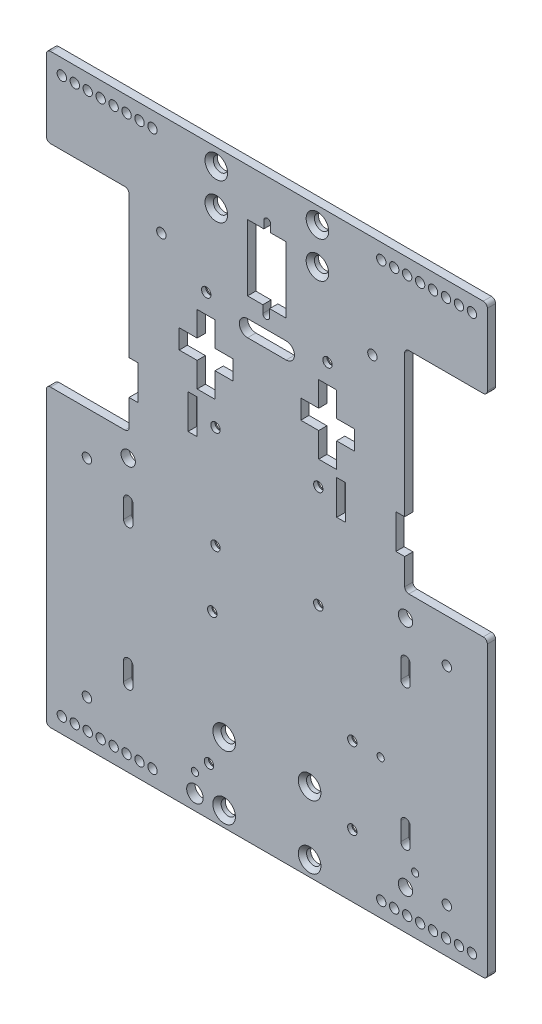
SolidWorks part; units mm, degrees
ref_plane "Front Plane" through (0, 0, 0) normal (0, 0, 1) x (1, 0, 0)
ref_plane "Top Plane" through (0, 0, 0) normal (0, 1, 0) x (1, 0, 0)
ref_plane "Right Plane" through (0, 0, 0) normal (1, 0, 0) x (0, 0, -1)
sketch "Sketch1" plane through (0, 0, 0) normal (0, 0, 1) x (1, 0, 0)
  line L0 (0, 103.7745) -> (0, -122.5392) construction
  line L1 (-241.098, -9.3824) -> (295.6863, -9.3824) construction
  line L2 (-80, -100.3627) -> (80, -100.3627)
  line L3 (80, -100.3627) -> (80, 6.6373)
  line L4 (80, 6.6373) -> (50, 6.6373)
  line L5 (50, 6.6373) -> (50, 83.1373)
  line L6 (50, 83.1373) -> (80, 83.1373)
  line L7 (80, 83.1373) -> (80, 112.1373)
  line L8 (80, 112.1373) -> (-80, 112.1373)
  line L9 (-80, -100.3627) -> (-80, 6.6373)
  line L10 (-80, 6.6373) -> (-50, 6.6373)
  line L11 (-50, 6.6373) -> (-50, 83.1373)
  line L12 (-50, 83.1373) -> (-80, 83.1373)
  line L13 (-80, 83.1373) -> (-80, 112.1373)
  point P14 (0, -100.3627)
  point P19 (0, 112.1373)
  dimension "D1" = 29
  dimension "D2" = 76.5
  dimension "D3" = 107
  dimension "D4" = 160
  dimension "D5" = 30
  dimension "D6" = 30
extrude "Boss-Extrude1" add sketch "Sketch1" along normal blind 3
sketch "Sketch2" plane through (0, 0, 0) normal (0, 0, -1) x (-1, 0, 0)
  line L0 (0, 75.1311) -> (0, 87.1311) construction
  line L1 (-133.8252, 10.7921) -> (150.4053, 10.7921) construction
  line L2 (-7, 95.0453) -> (-1.3739, 95.0453)
  line L3 (7, 95.0453) -> (7, 71.0453)
  line L4 (7, 71.0453) -> (1.4697, 71.0453)
  line L5 (-7, 95.0453) -> (-7, 71.0453)
  line L7 (-1.3739, 97.7783) -> (-1.3739, 95.0453)
  line L8 (1.0943, 97.7783) -> (1.0943, 95.0453)
  line L9 (0, 0) -> (0, 124.4997) construction
  line L10 (1.4697, 68.3124) -> (1.4697, 71.0453)
  line L11 (-0.9985, 68.3124) -> (-0.9985, 71.0453)
  line L12 (1.0943, 95.0453) -> (7, 95.0453)
  line L13 (-0.9985, 71.0453) -> (-7, 71.0453)
  arc A0 (1.0943, 97.7783) -> (-1.3739, 97.7783) centre (-0.1398, 97.7783) ccw
  arc A1 (1.4697, 68.3124) -> (-0.9985, 68.3124) centre (0.2356, 68.3124) cw
  circle A2 centre (38.2796, 75.1373) radius 1.7
  circle A3 centre (-38.2796, 75.1373) radius 1.7
  point P10 (0, 75.1373)
  point P11 (0, 99.1373)
  dimension "D2" = 14
  dimension "D3" = 24
extrude "Cut-Extrude1" cut sketch "Sketch2" against normal blind 3
sketch "Sketch3" plane through (0, 0, 3) normal (0, 0, 1) x (1, 0, 0)
  line L0 (0, 161.5948) -> (0, -130.4668) construction
  line L3 (-7, 60.8964) -> (7, 60.8964) construction
  line L4 (-7, 63.8964) -> (7, 63.8964)
  line L5 (-7, 57.8964) -> (7, 57.8964)
  circle A1 centre (-22, 64.6804) radius 1.7
  circle A2 centre (22, 64.6804) radius 1.7
  arc A3 (-7, 63.8964) -> (-7, 57.8964) centre (-7, 60.8964) ccw
  arc A4 (7, 57.8964) -> (7, 63.8964) centre (7, 60.8964) ccw
  point P15 (0, 60.8964)
  dimension "D2" = 44
  dimension "D3" = 14
extrude "Cut-Extrude2" cut sketch "Sketch3" against normal blind 3
sketch "Sketch4" plane through (0, 0, 3) normal (0, 0, 1) x (1, 0, 0)
  line L0 (0, 119.8519) -> (0, 60.8576) construction
  line L1 (80, 83.1373) -> (80, 112.1373) construction
  line L3 (80, 112.1373) -> (-80, 112.1373) construction
  line L4 (104.1126, 106.5373) -> (-21.9204, 106.5373) construction
  line L5 (-144.8224, 0) -> (150.0768, 0) construction
  line L6 (-113.8427, 6.6373) -> (99.251, 6.6373) construction
  line L7 (-80, -100.3627) -> (80, -100.3627) construction
  line L8 (-80, 6.6373) -> (-80, -100.3627) construction
  line L9 (-130.8506, -94.7627) -> (-23.3076, -94.7627) construction
  line L10 (-74.4, -94.7627) -> (-69.7, -94.7627) construction
  circle A0 centre (74.4, 106.5373) radius 1.7
  circle A1 centre (69.7, 106.5373) radius 1.7
  circle A2 centre (65, 106.5373) radius 1.7
  circle A3 centre (60.3, 106.5373) radius 1.7
  circle A4 centre (55.6, 106.5373) radius 1.7
  circle A5 centre (50.9, 106.5373) radius 1.7
  circle A6 centre (46.2, 106.5373) radius 1.7
  circle A7 centre (41.5, 106.5373) radius 1.7
  circle A8 centre (-74.4, 106.5373) radius 1.7
  circle A9 centre (-69.7, 106.5373) radius 1.7
  circle A10 centre (-65, 106.5373) radius 1.7
  circle A11 centre (-60.3, 106.5373) radius 1.7
  circle A12 centre (-55.6, 106.5373) radius 1.7
  circle A13 centre (-50.9, 106.5373) radius 1.7
  circle A14 centre (-46.2, 106.5373) radius 1.7
  circle A15 centre (-41.5, 106.5373) radius 1.7
  circle A16 centre (-74.4, -94.7627) radius 1.7
  circle A17 centre (-69.7, -94.7627) radius 1.7
  circle A18 centre (-65, -94.7627) radius 1.7
  circle A19 centre (-60.3, -94.7627) radius 1.7
  circle A20 centre (-55.6, -94.7627) radius 1.7
  circle A21 centre (-50.9, -94.7627) radius 1.7
  circle A22 centre (-46.2, -94.7627) radius 1.7
  circle A23 centre (-41.5, -94.7627) radius 1.7
  circle A24 centre (41.5, -94.7627) radius 1.7
  circle A25 centre (46.2, -94.7627) radius 1.7
  circle A26 centre (50.9, -94.7627) radius 1.7
  circle A27 centre (55.6, -94.7627) radius 1.7
  circle A28 centre (60.3, -94.7627) radius 1.7
  circle A29 centre (65, -94.7627) radius 1.7
  circle A30 centre (69.7, -94.7627) radius 1.7
  circle A31 centre (74.4, -94.7627) radius 1.7
  dimension "D1" = 5.6
  dimension "D2" = 5.6
  dimension "D3" = 8
  dimension "D4" = 5.6
  dimension "D5" = 5.6
  dimension "D6" = 8
extrude "Cut-Extrude3" cut sketch "Sketch4" against normal blind 3
sketch "Sketch6" plane through (0, 0, 0) normal (0, 0, 1) x (1, 0, 0)
  line L0 (0, 117.4623) -> (0, -109.6474) construction
  line L1 (142.8274, 0) -> (-149.0496, 0) construction
  line L2 (25.3, 57.6373) -> (18.8, 57.6373)
  line L3 (18.8, 57.6373) -> (18.8, 48.6373)
  line L4 (18.8, 48.6373) -> (12.3, 48.6373)
  line L5 (12.3, 48.6373) -> (12.3, 41.6373)
  line L6 (12.3, 41.6373) -> (18.8, 41.6373)
  line L7 (18.8, 41.6373) -> (18.8, 32.6373)
  line L8 (18.8, 32.6373) -> (25.3, 32.6373)
  line L9 (25.3, 32.6373) -> (25.3, 41.6373)
  line L10 (25.3, 41.6373) -> (31.8, 41.6373)
  line L11 (31.8, 41.6373) -> (31.8, 48.6373)
  line L12 (31.8, 48.6373) -> (25.3, 48.6373)
  line L13 (25.3, 48.6373) -> (25.3, 57.6373)
  line L14 (80, 112.1373) -> (-80, 112.1373) construction
  line L15 (-31.8, 48.6373) -> (-25.3, 48.6373)
  line L16 (22.05, 25.7267) -> (22.05, 72.8258) construction
  line L17 (39.5883, 45.1373) -> (1.8205, 45.1373) construction
  line L18 (-31.8, 41.6373) -> (-31.8, 48.6373)
  line L19 (-25.3, 41.6373) -> (-31.8, 41.6373)
  line L20 (-25.3, 32.6373) -> (-25.3, 41.6373)
  line L21 (-18.8, 32.6373) -> (-25.3, 32.6373)
  line L22 (-18.8, 41.6373) -> (-18.8, 32.6373)
  line L23 (-12.3, 41.6373) -> (-18.8, 41.6373)
  line L24 (-12.3, 48.6373) -> (-12.3, 41.6373)
  line L25 (-18.8, 48.6373) -> (-12.3, 48.6373)
  line L26 (-18.8, 57.6373) -> (-18.8, 48.6373)
  line L27 (-25.3, 57.6373) -> (-18.8, 57.6373)
  line L28 (-25.3, 48.6373) -> (-25.3, 57.6373)
  line L29 (50, 6.6373) -> (50, 83.1373) construction
  dimension "D1" = 54.5
  dimension "D2" = 25
  dimension "D3" = 19.5
  dimension "D4" = 6.5
  dimension "D5" = 6.5
  dimension "D6" = 7
  dimension "D7" = 24.7
extrude "Cut-Extrude6" cut sketch "Sketch6" along normal blind 3
fillet "Fillet1" radius 1.5 4 edges at (80, 83.1373, 1.5) (80, 112.1373, 1.5) (-80, 112.1373, 1.5) (-80, 83.1373, 1.5)
fillet "Fillet2" radius 1.5 2 edges at (80, -100.3627, 1.5) (-80, -100.3627, 1.5)
sketch "Sketch7" plane through (0, 0, 3) normal (0, 0, 1) x (1, 0, 0)
  line L0 (0, 119.4421) -> (0, -115.5867) construction
  line L1 (-78.5, -100.3627) -> (78.5, -100.3627) construction
  circle A0 centre (-15.5, -94.8627) radius 2.6
  circle A1 centre (-15.5, -71.8627) radius 2.6
  circle A2 centre (15.5, -94.8627) radius 2.6
  circle A3 centre (15.5, -71.8627) radius 2.6
  dimension "D1" = 5.5
  dimension "D2" = 23
  dimension "D4" = 31
  dimension "D5" = 5.2
  dimension "D6" = 5.2
  dimension "D3" = 31
extrude "Cut-Extrude7" cut sketch "Sketch7" against normal blind 3
sketch "Sketch8" plane through (0, 0, 0) normal (0, 0, 1) x (1, 0, 0)
  line L0 (-50, 30.1373) -> (-46.8, 30.1373)
  line L1 (-50, 83.1373) -> (-50, 6.6373) construction
  line L2 (-46.8, 30.1373) -> (-46.8, 17.6373)
  line L3 (-46.8, 17.6373) -> (-50, 17.6373)
  line L4 (-50, 17.6373) -> (-50, 30.1373)
  line L5 (-50, 6.6373) -> (-80, 6.6373) construction
  line L6 (0, 37.5967) -> (0, -16.6739) construction
  line L7 (46.8, 17.6373) -> (50, 17.6373)
  line L8 (50, 30.1373) -> (46.8, 30.1373)
  line L9 (50, 17.6373) -> (50, 30.1373)
  line L10 (46.8, 30.1373) -> (46.8, 17.6373)
  line L11 (-50, 23.8873) -> (-9.1631, 23.8873) construction
  dimension "D1" = 11
  dimension "D2" = 12.5
  dimension "D3" = 3.2
extrude "Cut-Extrude9" cut sketch "Sketch8" along normal blind 3
sketch "Sketch9" plane through (0, 0, 3) normal (0, 0, 1) x (1, 0, 0)
  line L0 (0, 47.1979) -> (0, -24.6531) construction
  line L1 (-46.8, 23.8873) -> (46.8, 23.8873) construction
  line L2 (-46.8, 17.6373) -> (-46.8, 30.1373) construction
  line L3 (46.8, 30.1373) -> (46.8, 17.6373) construction
  line L4 (-46.8, 30.1373) -> (46.8, 30.1373) construction
  line L5 (-46.8, 17.6373) -> (46.8, 17.6373) construction
  line L6 (-28.6, 30.1373) -> (-28.6, 17.6373)
  line L7 (-28.6, 17.6373) -> (-25.35, 17.6373)
  line L8 (-25.35, 17.6373) -> (-25.35, 30.1373)
  line L9 (-25.35, 30.1373) -> (-28.6, 30.1373)
  line L10 (28.6, 17.6373) -> (25.35, 17.6373)
  line L11 (25.35, 17.6373) -> (25.35, 30.1373)
  line L12 (25.35, 30.1373) -> (28.6, 30.1373)
  line L13 (28.6, 30.1373) -> (28.6, 17.6373)
  dimension "D1" = 3.25
  dimension "D2" = 18.2
extrude "Cut-Extrude10" cut sketch "Sketch9" against normal blind 3
sketch "Sketch10" plane through (0, 0, 0) normal (0, 0, 1) x (1, 0, 0)
  line L0 (0, 32.0487) -> (0, -85.0415) construction
  line L1 (-112.565, 0) -> (146.2213, 0) construction
  line L2 (-80, 6.6373) -> (-80, -98.8627) construction
  line L3 (-50.3, -15.0627) -> (-50.3, -21.6627) construction
  line L4 (-48.6, -15.0627) -> (-48.6, -21.6627)
  line L5 (-52, -15.0627) -> (-52, -21.6627)
  line L6 (-50, 32.1373) -> (-50, -164.0413) construction
  line L7 (-52, -66.0627) -> (-52, -72.6627)
  line L8 (-50, 6.6373) -> (-80, 6.6373) construction
  line L9 (-48.6, -66.0627) -> (-48.6, -72.6627)
  line L10 (-50.3, -66.0627) -> (-50.3, -72.6627) construction
  line L11 (-50, 83.1373) -> (-50, 32.1373) construction
  line L12 (50.3, -66.0627) -> (50.3, -72.6627) construction
  line L13 (48.6, -66.0627) -> (48.6, -72.6627)
  line L14 (52, -66.0627) -> (52, -72.6627)
  line L15 (50.3, -15.0627) -> (50.3, -21.6627) construction
  line L16 (48.6, -15.0627) -> (48.6, -21.6627)
  line L17 (52, -15.0627) -> (52, -21.6627)
  arc A0 (-48.6, -15.0627) -> (-52, -15.0627) centre (-50.3, -15.0627) ccw
  arc A1 (-52, -21.6627) -> (-48.6, -21.6627) centre (-50.3, -21.6627) ccw
  arc A2 (-48.6, -66.0627) -> (-52, -66.0627) centre (-50.3, -66.0627) ccw
  arc A3 (-52, -72.6627) -> (-48.6, -72.6627) centre (-50.3, -72.6627) ccw
  arc A4 (48.6, -66.0627) -> (52, -66.0627) centre (50.3, -66.0627) cw
  arc A5 (52, -72.6627) -> (48.6, -72.6627) centre (50.3, -72.6627) cw
  arc A6 (48.6, -15.0627) -> (52, -15.0627) centre (50.3, -15.0627) cw
  arc A7 (52, -21.6627) -> (48.6, -21.6627) centre (50.3, -21.6627) cw
  point P10 (-50.3, -18.3627)
  point P23 (-50.3, -69.3627)
  point P30 (50.3, -69.3627)
  point P37 (50.3, -18.3627)
  dimension "D1" = 20
  dimension "D2" = 10
  dimension "D5" = 28
  dimension "D4" = 51
  dimension "D6" = 3.4
  dimension "D3" = 2
extrude "Cut-Extrude12" cut sketch "Sketch10" along normal blind 3
sketch "Sketch11" plane through (0, 0, 0) normal (0, 0, 1) x (1, 0, 0)
  line L0 (0, 120.896) -> (0, -114.7225) construction
  line L1 (-147.8474, 0) -> (160.9193, 0) construction
  line L2 (-25.35, 23.8873) -> (25.35, 23.8873) construction
  line L3 (-25.35, 17.6373) -> (-25.35, 30.1373) construction
  line L4 (25.35, 30.1373) -> (25.35, 17.6373) construction
  circle A0 centre (-18.65, 23.8873) radius 1.7
  circle A1 centre (-18.65, -13.3127) radius 1.7
  circle A2 centre (18.65, -13.3127) radius 1.7
  circle A3 centre (18.65, 23.8873) radius 1.7
  dimension "D1" = 5
  dimension "D2" = 3.4
  dimension "D3" = 5
extrude "Cut-Extrude14" cut sketch "Sketch11" along normal blind 3
sketch "Sketch12" plane through (0, 0, 0) normal (0, 0, 1) x (1, 0, 0)
  line L0 (0, 118.5936) -> (0, -114.7383) construction
  line L1 (-119.07, 1.9277) -> (166.0192, 1.9277) construction
  line L4 (80, 6.6373) -> (50, 6.6373) construction
  line L6 (80, -98.8627) -> (80, 6.6373) construction
  line L7 (-78.5, -100.3627) -> (78.5, -100.3627) construction
  circle A0 centre (65.3, -9.0627) radius 1.7
  circle A1 centre (-65.3, -9.0627) radius 1.7
  circle A2 centre (65.3, -84.1627) radius 1.7
  circle A3 centre (-65.3, -84.1627) radius 1.7
  dimension "D1" = 14
  dimension "D2" = 13
  dimension "D3" = 13
  dimension "D4" = 14.5
extrude "Cut-Extrude16" cut sketch "Sketch12" along normal blind 3
sketch "Sketch13" plane through (0, 0, 0) normal (0, 0, 1) x (1, 0, 0)
  line L0 (0, 95.119) -> (0, -115.5867) construction
  line L1 (-133.2113, 0) -> (163.1909, 0) construction
  line L3 (-78.5, -100.3627) -> (78.5, -100.3627) construction
  line L4 (-80, 6.6373) -> (-80, -98.8627) construction
  circle A0 centre (-21, -82.8627) radius 1.7
  circle A2 centre (31, -77.6627) radius 1.7
  circle A3 centre (31, -49.7627) radius 1.7
  circle A4 centre (-19.8, -34.5627) radius 1.7
  dimension "D1" = 17.5
  dimension "D3" = 5.2
  dimension "D5" = 27.9
  dimension "D6" = 50.8
  dimension "D2" = 59
  dimension "D4" = 52
  dimension "D7" = 48.3
extrude "Cut-Extrude18" cut sketch "Sketch13" along normal blind 3
sketch "Sketch14" plane through (0, 0, 0) normal (0, 0, 1) x (1, 0, 0)
  line L0 (0, 14.3859) -> (0, -107.2008) construction
  line L3 (80, -98.8627) -> (80, 6.6373) construction
  circle A1 centre (53.8, -79.7627) radius 1.3
  circle A2 centre (41.3, -49.7627) radius 1.3
  dimension "D1" = 40
  dimension "D2" = 30
  dimension "D3" = 12.5
extrude "Cut-Extrude20" cut sketch "Sketch14" along normal blind 3
sketch "Sketch15" plane through (0, 0, 0) normal (0, 0, 1) x (1, 0, 0)
  line L0 (0, 37.8305) -> (0, -61.1397) construction
  line L1 (-57.516, 0) -> (91.2068, 0) construction
  line L2 (50.3, -23.3627) -> (50.3, -64.3627) construction
  line L3 (50.3, -43.8627) -> (-40.3092, -43.8627) construction
  line L4 (50.3, -23.3627) -> (50.3, 36.7606) construction
  line L5 (50.3, -13.3627) -> (101.0147, -13.3627) construction
  arc A0 (48.6, -21.6627) -> (52, -21.6627) centre (50.3, -21.6627) ccw construction
  circle A1 centre (50.3, -1.5627) radius 2.6
  arc A2 (52, -15.0627) -> (48.6, -15.0627) centre (50.3, -15.0627) ccw construction
  circle A3 centre (-50.3, -1.5627) radius 2.6
  arc A4 (52, -66.0627) -> (48.6, -66.0627) centre (50.3, -66.0627) ccw construction
  circle A5 centre (50.3, -86.1627) radius 2.6
  dimension "D1" = 9.2
extrude "Cut-Extrude21" cut sketch "Sketch15" along normal blind 10
sketch "Sketch16" plane through (0, 0, 3) normal (0, 0, 1) x (1, 0, 0)
  line L0 (-15.5, -94.8627) -> (-15.5, -30.8074) construction
  line L1 (-18.1, -94.8627) -> (-18.1, -49.3742) construction
  line L2 (-26.1, -91.8627) -> (-4.2475, -91.8627) construction
  circle A0 centre (-15.5, -94.8627) radius 2.6 construction
  circle A1 centre (-26.1, -94.8627) radius 3
  circle A2 centre (-26.1, -88.0627) radius 1.3
  dimension "D1" = 5
  dimension "D2" = 2.5
extrude "Cut-Extrude24" cut sketch "Sketch16" against normal blind 10
chamfer "Chamfer1" distance 1.5 angle 45 1 edges at (-12.9, -71.8627, 3)
chamfer "Chamfer2" distance 1.5 angle 45 1 edges at (12.9, -71.8627, 3)
chamfer "Chamfer3" distance 1.5 angle 45 1 edges at (-12.9, -94.8627, 3)
chamfer "Chamfer4" distance 1.5 angle 45 1 edges at (12.9, -94.8627, 3)
chamfer "Chamfer5" distance 1.5 angle 45 1 edges at (20.35, 23.8873, 0)
chamfer "Chamfer6" distance 1.5 angle 45 1 edges at (-16.95, 23.8873, 0)
chamfer "Chamfer7" distance 1.5 angle 45 1 edges at (20.35, -13.3127, 0)
chamfer "Chamfer8" distance 1.5 angle 45 1 edges at (-16.95, -13.3127, 0)
chamfer "Chamfer9" distance 1.5 angle 45 1 edges at (-18.1, -34.5627, 0)
chamfer "Chamfer10" distance 1.5 angle 45 1 edges at (32.7, -49.7627, 0)
chamfer "Chamfer11" distance 1.5 angle 45 1 edges at (32.7, -77.6627, 0)
chamfer "Chamfer12" distance 1.5 angle 45 1 edges at (-19.3, -82.8627, 0)
sketch "Sketch17" plane through (0, 0, 0) normal (0, 0, 1) x (1, 0, 0)
  line L0 (0, 228.2407) -> (0, 55.0266) construction
  line L1 (-113.4269, 141.6336) -> (115.0781, 141.6336) construction
  line L2 (41.5, 106.5373) -> (41.5, 201.3982) construction
  line L3 (-41.5, 106.5373) -> (-41.5, 205.9867) construction
  line L4 (-46.2, 106.5373) -> (-46.2, 205.9867) construction
  line L5 (46.2, 106.5373) -> (46.2, 201.3982) construction
  line L6 (0, 112.1373) -> (0, 87.6373) construction
  line L7 (78.5, 112.1373) -> (-78.5, 112.1373) construction
  line L8 (-18.35, 103.4373) -> (17.8418, 103.4373) construction
  circle A0 centre (-18.35, 106.0373) radius 2.6
  circle A1 centre (-18.35, 92.8373) radius 2.6
  circle A2 centre (18.35, 92.8373) radius 2.6
  circle A3 centre (18.35, 106.0373) radius 2.6
  dimension "D1" = 24.5
  dimension "D2" = 3.5
  dimension "D3" = 8
  dimension "D4" = 15.75
extrude "Cut-Extrude27" cut sketch "Sketch17" along normal blind 10
fillet "Fillet3" radius 1.5 1 edges at (80, 6.6373, 1.5)
fillet "Fillet4" radius 1.5 1 edges at (-80, 6.6373, 1.5)
chamfer "Chamfer13" distance 1.5 angle 45 1 edges at (-15.75, 106.0373, 3)
chamfer "Chamfer14" distance 1.5 angle 45 1 edges at (20.95, 106.0373, 3)
chamfer "Chamfer15" distance 1.5 angle 45 1 edges at (-15.75, 92.8373, 3)
chamfer "Chamfer16" distance 1.5 angle 45 1 edges at (20.95, 92.8373, 3)
chamfer "Chamfer17" distance 1.5 angle 45 1 edges at (-20.3, 64.6804, 0)
chamfer "Chamfer18" distance 1.5 angle 45 1 edges at (20.3, 64.6804, 0)
fillet "Fillet5" radius 1.5 1 edges at (50, 6.6373, 1.5)
fillet "Fillet6" radius 1.5 1 edges at (50, 83.1373, 1.5)
fillet "Fillet7" radius 1.5 1 edges at (-50, 83.1373, 1.5)
fillet "Fillet8" radius 1.5 1 edges at (-50, 6.6373, 1.5)
